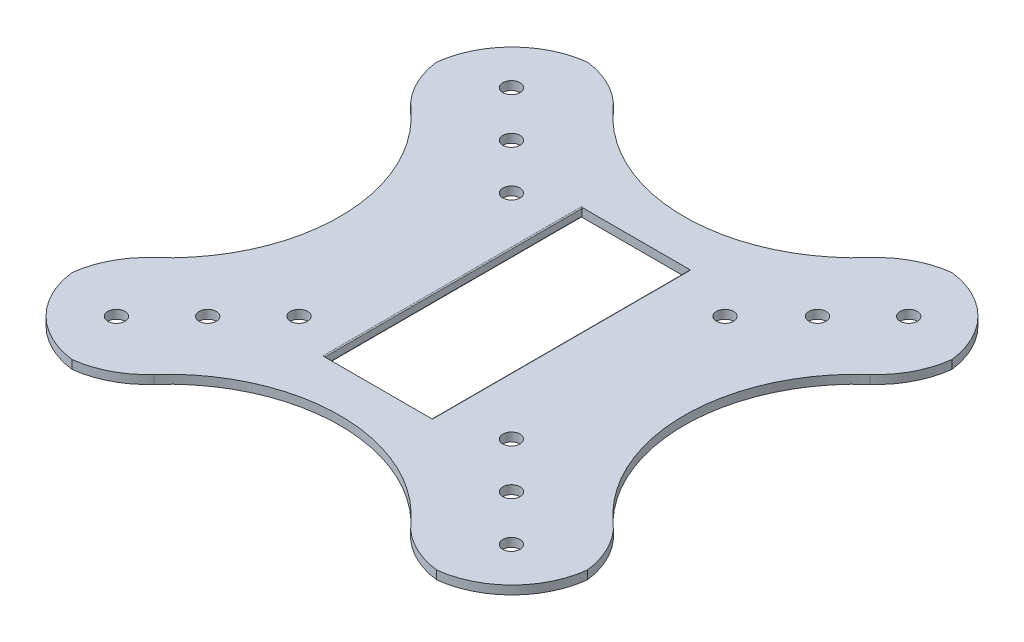
SolidWorks part; units mm, degrees
material "AISI 1020 Steel, Cold Rolled"
ref_plane "Front Plane" through (0, 0, 0) normal (0, 0, 1) x (1, 0, 0)
ref_plane "Top Plane" through (0, 0, 0) normal (0, 1, 0) x (1, 0, 0)
ref_plane "Right Plane" through (0, 0, 0) normal (1, 0, 0) x (0, 0, -1)
sketch "Sketch1" plane through (0, 0, 0) normal (0, 1, 0) x (1, 0, 0)
  line L1 (-60, 60) -> (60, 60)
  line L2 (-60, 60) -> (-60, -60)
  line L3 (-60, -60) -> (60, -60)
  line L4 (60, 60) -> (60, -60)
  line L5 (-60, 60) -> (60, -60) construction
  line L6 (-60, -60) -> (60, 60) construction
  point P0 (0, 0)
  dimension "D1" = 120
  dimension "D2" = 120
extrude "Boss-Extrude1" add sketch "Sketch1" along normal blind 2
sketch "Sketch2" plane through (0, 2, 0) normal (0, 1, 0) x (1, 0, 0)
  circle A0 centre (-80, 0) radius 40
  circle A1 centre (80, 0) radius 40
  circle A2 centre (0, 80) radius 40
  circle A3 centre (0, -80) radius 40
  dimension "D1" = 80
extrude "Cut-Extrude1" cut sketch "Sketch2" against normal through all
fillet "Fillet1" radius 20 12 edges at (60, 1, -34.641) (60, 1, -60) (34.641, 1, -60) (-34.641, 1, -60) (-60, 1, -60) (-60, 1, -34.641) (-60, 1, 34.641) (-60, 1, 60) (-34.641, 1, 60) (34.641, 1, 60) (60, 1, 34.641) (60, 1, 60)
sketch "Sketch3" plane through (0, 2, 0) normal (0, 1, 0) x (1, 0, 0)
  line L0 (64.4947, 64.3691) -> (-66.7464, -66.873) construction
  line L1 (-65.6161, 65.4858) -> (65.6246, -65.7568) construction
  circle A0 centre (24.8116, 24.6857) radius 2
  circle A1 centre (35.5523, 35.4265) radius 2
  circle A2 centre (46.1589, 46.0332) radius 2
  circle A3 centre (-24.8141, 24.6832) radius 2
  circle A4 centre (-24.6855, -24.8118) radius 2
  circle A5 centre (24.6829, -24.8144) radius 2
  circle A6 centre (-35.4206, 35.2899) radius 2
  circle A7 centre (-46.0272, 45.8966) radius 2
  circle A8 centre (-35.2921, -35.4184) radius 2
  circle A9 centre (-45.8987, -46.0251) radius 2
  circle A10 centre (35.2894, -35.4211) radius 2
  circle A11 centre (45.8959, -46.0278) radius 2
  dimension "D1" = 35
  dimension "D2" = 35
  dimension "D3" = 35
  dimension "D4" = 35
extrude "Cut-Extrude2" cut sketch "Sketch3" against normal through all
sketch "Sketch4" plane through (0, 2, 0) normal (0, 1, 0) x (1, 0, 0)
  line L0 (-13.7162, -30) -> (11.2838, -30)
  line L1 (11.2838, 30) -> (-13.7162, 30)
  line L2 (-13.7162, 30) -> (-13.7162, -30)
  line L4 (11.2838, 30) -> (11.2838, -30)
  point P0 (0, 0)
  dimension "D1" = 25
sketch "Sketch7" plane through (0, 2, 0) normal (0, 1, 0) x (1, 0, 0)
  line L0 (0, 15.8003) -> (0, -14.1997) construction
  line L1 (5, 15.8003) -> (5, -14.1997)
  line L2 (-5, 15.8003) -> (-5, -14.1997)
  arc A0 (5, 15.8003) -> (-5, 15.8003) centre (0, 15.8003) ccw
  arc A1 (-5, -14.1997) -> (5, -14.1997) centre (0, -14.1997) ccw
  point P3 (0, 0.8003)
  dimension "D1" = 15
  dimension "D2" = 10
extrude "Cut-Extrude5" cut sketch "Sketch7" against normal blind 2
ref_plane "Plane1" through (0, 10, 0) normal (0, 1, 0) x (1, 0, 0)
extrude "Cut-Extrude6" cut sketch "Sketch4" against normal blind 10 contours L1 L2 L0 L4
fillet "Fillet2" radius 0.25 4 edges at (11.2838, 0, 0) (11.2838, 2, 0) (-13.7162, 0, 0) (-13.7162, 2, 0)
